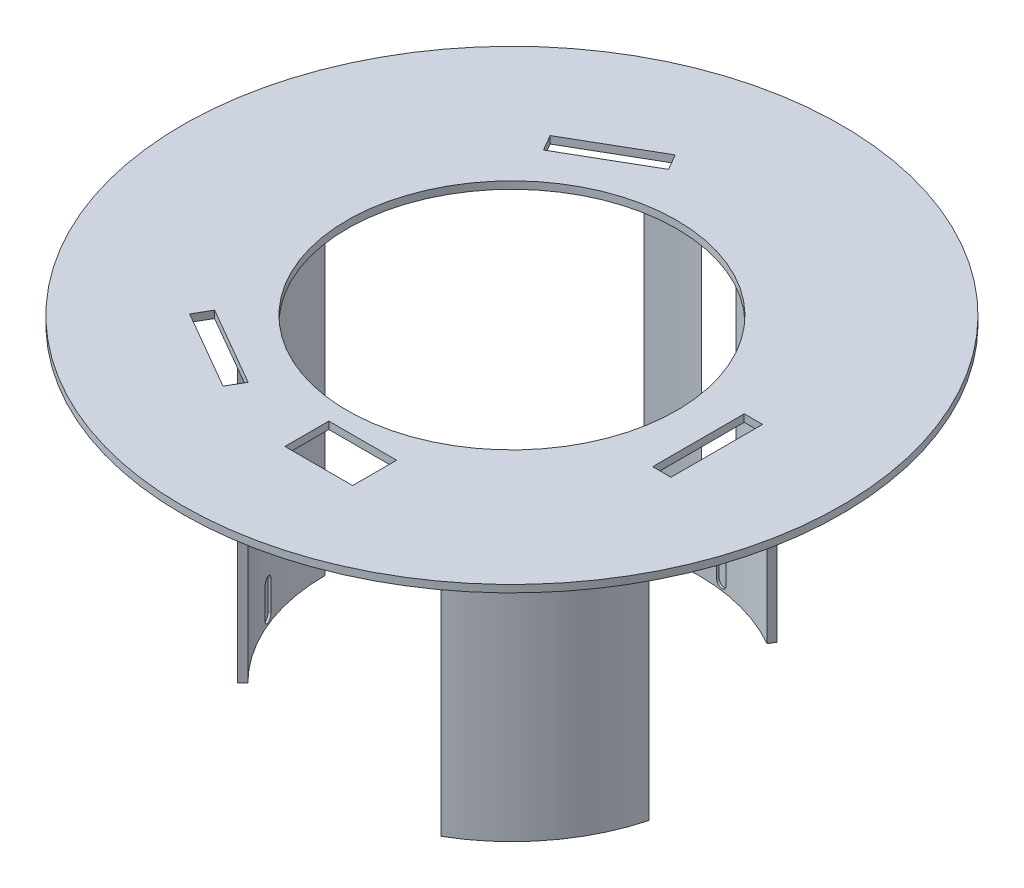
SolidWorks part; units mm, degrees
ref_plane "Front Plane" through (0, 0, 0) normal (0, 0, 1) x (1, 0, 0)
ref_plane "Top Plane" through (0, 0, 0) normal (0, 1, 0) x (1, 0, 0)
ref_plane "Right Plane" through (0, 0, 0) normal (1, 0, 0) x (0, 0, -1)
sketch "Sketch3" plane through (0, 0, 0) normal (0, 1, 0) x (1, 0, 0)
  circle A0 centre (0, 0) radius 90
  dimension "D1" = 180
extrude "Boss-Extrude3" add sketch "Sketch3" along normal blind 2
sketch "Sketch4" plane through (0, 0, 0) normal (0, -1, 0) x (1, 0, 0)
  circle A0 centre (0, 0) radius 45
  dimension "D1" = 90
extrude "Cut-Extrude1" cut sketch "Sketch4" against normal blind 2
sketch "Sketch6" plane through (0, 0, 0) normal (0, -1, 0) x (1, 0, 0)
  line L0 (0, 0) -> (-53, 0)
  line L1 (0, 0) -> (-37.4767, 37.4767)
  arc A0 (-37.4767, 37.4767) -> (-53, 0) centre (0, 0) ccw
  arc A1 (-31.8198, 31.8198) -> (-45, 0) centre (0, 0) ccw
  arc A2 (-32.5269, 32.5269) -> (-46, 0) centre (0, 0) ccw
  arc A3 (-36.0624, 36.0624) -> (-51, 0) centre (0, 0) ccw
  circle M1 centre (0, 0) radius 45
  dimension "D1" = 1
  dimension "D2" = 5
  dimension "D3" = 2
  dimension "D4" = 45
extrude "Boss-Extrude4" add sketch "Sketch6" along normal blind 85 contours A2 M1 region at (-45.5, 0, 0.3548)
extrude "Boss-Extrude5" add sketch "Sketch6<3>" along normal blind 85 contours A0 A3 region at (-52, 0, 0.4113)
sketch "Sketch6<3>" plane through (0, 0, 0) normal (0, -1, 0) x (1, 0, 0) same geometry as "Sketch6"
ref_plane "Plane4" through (-38.4099, 0, 15.9099) normal (0.9239, 0, -0.3827) x (-0.3827, 0, -0.9239)
sketch "Sketch14" plane through (-38.4099, 0, 15.9099) normal (0.9239, 0, -0.3827) x (-0.3827, 0, -0.9239)
  line L0 (0, 0) -> (0, -85) construction
  line L1 (1.5, -75) -> (1.5, -83)
  line L2 (-1.5, -75) -> (-1.5, -83)
  line L4 (20.2822, 0) -> (-20.2822, 0)
  line L5 (20.2822, -85) -> (20.2822, 0)
  line L6 (-20.2822, -85) -> (20.2822, -85)
  line L7 (-20.2822, 0) -> (-20.2822, -85)
  line L8 (20.2822, 0) -> (-20.2822, 0) construction
  line L9 (20.2822, -85) -> (20.2822, 0) construction
  line L10 (-20.2822, -85) -> (20.2822, -85) construction
  line L11 (-20.2822, 0) -> (-20.2822, -85) construction
  arc A0 (-1.5, -83) -> (1.5, -83) centre (0, -83) ccw
  arc A1 (1.5, -75) -> (-1.5, -75) centre (0, -75) ccw
  dimension "D2" = 3
  dimension "D3" = 2
  dimension "D4" = 8
  dimension "D1" = 0
extrude "Cut-Extrude9" cut sketch "Sketch14" against normal blind 10 contours A0 L1 A1 L2
pattern_circular "CirPattern4" count 3 over 360 about axis through (0, 0, 0) along (0, 1, 0) of "Boss-Extrude5", "Cut-Extrude9", "Boss-Extrude4"
sketch "Sketch11" plane through (0, 0, 0) normal (0, -1, 0) x (1, 0, 0)
  line L0 (-6.7476, -52.4795) -> (11.4066, -48.9193)
  line L1 (-6.7476, -52.4795) -> (-4.4382, -64.2552)
  line L2 (11.4066, -48.9193) -> (13.716, -60.695)
  line L3 (-4.4382, -64.2552) -> (13.716, -60.695)
  dimension "D1" = 12
extrude "Cut-Extrude5" cut sketch "Sketch11" against normal mid plane 120
sketch "Sketch15" plane through (0, 2, 0) normal (0, 1, 0) x (1, 0, 0)
  line L1 (55, 8.4328) -> (60, 8.4328)
  line L2 (55, 8.4328) -> (55, -16.5672)
  line L3 (55, -16.5672) -> (60, -16.5672)
  line L4 (60, 8.4328) -> (60, -16.5672)
  circle A0 centre (0, 0) radius 45 construction
  dimension "D1" = 55
  dimension "D2" = 5
  dimension "D3" = 25
extrude "Cut-Extrude10" cut sketch "Sketch15" against normal through all
pattern_circular "CirPattern5" count 3 over 360 about axis through (0, 2, 0) along (0, -1, 0) of "Cut-Extrude10"
sketch "Sketch16" plane through (0, -85, 0) normal (0, -1, 0) x (1, 0, 0)
  circle A0 centre (0, 0) radius 46
extrude "Cut-Extrude11" cut sketch "Sketch16" against normal up to surface (85 mm away) up to face at (-32.2723, 0, 47.7629)
sketch "Sketch17" plane through (0, 2, 0) normal (0, 1, 0) x (1, 0, 0)
  line L0 (13.716, 60.695) -> (-4.4382, 64.2552) construction
  line L1 (13.716, 60.695) -> (-4.4382, 64.2552)
  line L2 (11.4066, 48.9193) -> (13.716, 60.695) construction
  line L3 (11.4066, 48.9193) -> (13.716, 60.695)
  line L4 (-6.7476, 52.4795) -> (11.4066, 48.9193) construction
  line L5 (-6.7476, 52.4795) -> (11.4066, 48.9193)
  line L6 (-4.4382, 64.2552) -> (-6.7476, 52.4795) construction
  line L7 (-4.4382, 64.2552) -> (-6.7476, 52.4795)
extrude "Boss-Extrude6" add sketch "Sketch17" against normal up to surface (2 mm away) up to face at (-32.2723, 0, 47.7629)
sketch "Sketch18" plane through (0, 2, 0) normal (0, 1, 0) x (1, 0, 0)
  line L0 (0, 0) -> (-45, 0) construction
  line L1 (0, -50) -> (18.5, -50)
  line L2 (0, -50) -> (0, -62)
  line L3 (0, -62) -> (18.5, -62)
  line L4 (18.5, -50) -> (18.5, -62)
  line L5 (0, -50) -> (18.5, -62) construction
  line L6 (0, -62) -> (18.5, -50) construction
  circle A0 centre (0, 0) radius 45 construction
  point P0 (9.25, -56)
  dimension "D1" = 50
  dimension "D2" = 12
  dimension "D3" = 18.5
  dimension "D4" = 0
extrude "Cut-Extrude12" cut sketch "Sketch18" against normal up to surface (2 mm away) up to face at (-7.9293, 0, -51.4212)
